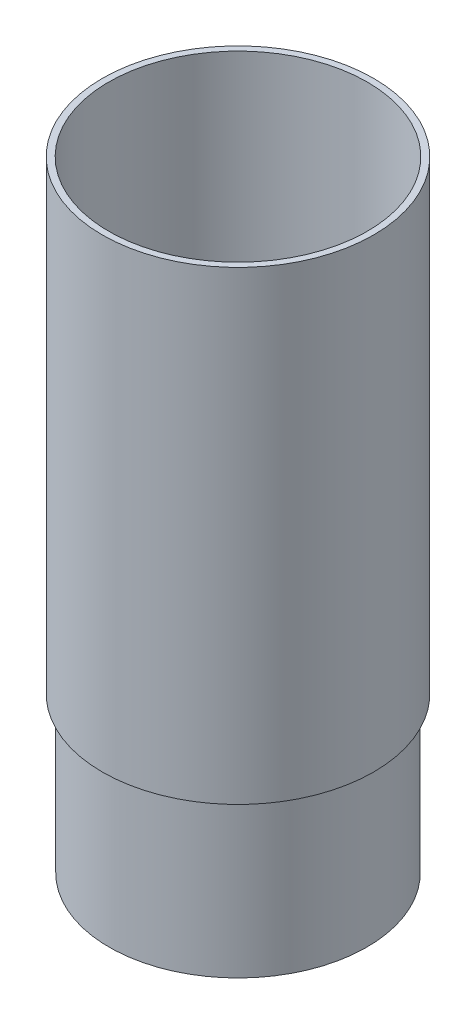
SolidWorks part; units mm, degrees
material "ABS"
ref_plane "Front Plane" through (0, 0, 0) normal (0, 0, 1) x (1, 0, 0)
ref_plane "Top Plane" through (0, 0, 0) normal (0, 1, 0) x (1, 0, 0)
ref_plane "Right Plane" through (0, 0, 0) normal (1, 0, 0) x (0, 0, -1)
sketch "Sketch1" plane through (0, 0, 0) normal (0, 0, 1) x (1, 0, 0)
  line L0 (0, 0) -> (0, 54.0332) construction
  line L1 (-20.0787, -6.8588) -> (-20.0787, 20.445)
  line L2 (-20.0787, 20.445) -> (-21.1836, 24.5685)
  line L3 (-21.1836, 24.5685) -> (-21.1836, 94.7412)
  line L4 (-21.1836, 94.7412) -> (-22.225, 94.7412)
  line L5 (-22.225, 94.7412) -> (-22.225, 18.5412)
  line L6 (-22.225, 18.5412) -> (-21.1201, 18.5412)
  line L7 (-21.1201, 18.5412) -> (-21.1201, -6.8588)
  line L8 (-21.1201, -6.8588) -> (-20.0787, -6.8588)
  dimension "D1" = 42.2402
  dimension "D2" = 44.45
  dimension "D3" = 25.4
  dimension "D4" = 101.6
  dimension "D5" = 1.0414
  dimension "D6" = 1.0414
  dimension "D7" = 15
revolve "Revolve1" add sketch "Sketch1" angle 360 mid plane about L0
